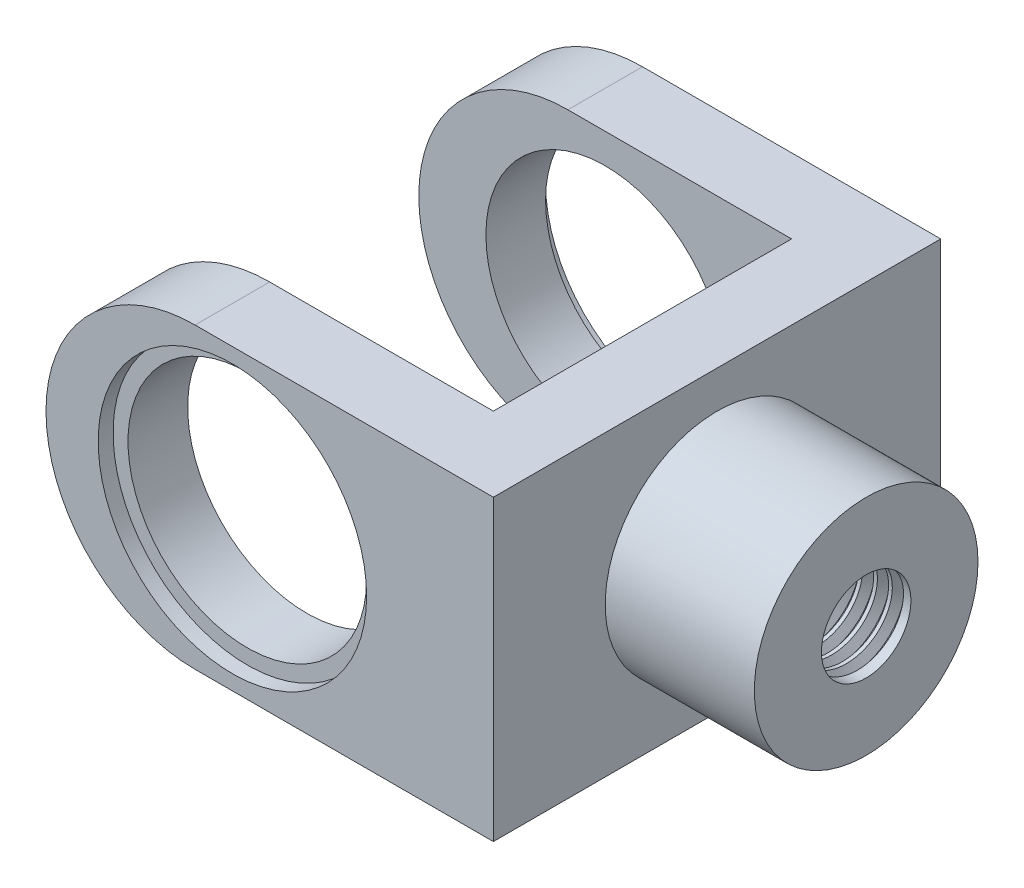
SolidWorks part; units mm, degrees
material "7075-T6 (SN)"
ref_plane "Ön Düzlem" through (0, 0, 0) normal (0, 0, 1) x (1, 0, 0)
ref_plane "Üst Düzlem" through (0, 0, 0) normal (0, 1, 0) x (1, 0, 0)
ref_plane "Sağ Düzlem" through (0, 0, 0) normal (1, 0, 0) x (0, 0, -1)
sketch "Çizim1" plane through (0, 0, 0) normal (0, 0, 1) x (1, 0, 0)
  line L0 (0, 10) -> (20, 10)
  line L1 (0, -10) -> (20, -10)
  line L2 (20, -10) -> (20, 10)
  line L3 (20, 0) -> (0, 0) construction
  line L4 (15, 10) -> (15, -10) construction
  arc A0 (0, 10) -> (0, -10) centre (0, 0) ccw
  circle A1 centre (2.5, 0) radius 4
  dimension "D1" = 20
  dimension "D2" = 20
  dimension "D3" = 8
  dimension "D4" = 5
  dimension "D5" = 12.5
extrude "Yükseklik-Ekstrüzyon1" add sketch "Çizim1" along normal blind 30
sketch "Çizim2" plane through (20, 0, 0) normal (1, 0, 0) x (0, 0, -1)
  line L2 (-25, -10) -> (-25, 10)
  line L3 (-25, -10) -> (-25, 10)
  line L4 (-25, 10) -> (-5, 10)
  line L5 (-5, -10) -> (-5, 10)
  line L6 (-5, -10) -> (-5, 10)
  line L7 (-25, -10) -> (-5, -10)
  dimension "D1" = 5
  dimension "D2" = 5
extrude "Kes-Ekstrüzyon1" cut sketch "Çizim2" against normal blind 51
sketch "Çizim3" plane through (20, 0, 0) normal (1, 0, 0) x (0, 0, -1)
  line L0 (-30, 10) -> (0, 10)
  line L1 (0, 10) -> (0, -10)
  line L2 (0, -10) -> (-30, -10)
  line L3 (-30, -10) -> (-30, 10)
extrude "Yükseklik-Ekstrüzyon2" add sketch "Çizim3" against normal blind 5
sketch "Çizim4" plane through (20, 0, 0) normal (1, 0, 0) x (0, 0, -1)
  line L0 (0, -10) -> (-30, 10) construction
  circle A0 centre (-15, 0) radius 3 construction
  circle A1 centre (-15, 0) radius 7.5
  dimension "D1" = 6
  dimension "D2" = 15
extrude "Yükseklik-Ekstrüzyon3" add sketch "Çizim4" along normal blind 10
sketch "Çizim7" plane through (30, 0, 0) normal (1, 0, 0) x (0, 0, -1)
  circle A0 centre (-15, 0) radius 3
  dimension "D1" = 6
extrude "Kes-Ekstrüzyon2" cut sketch "Çizim7" against normal blind 10
sketch "Sketch1" plane through (0, 0, 30) normal (0, 0, 1) x (1, 0, 0)
  circle A0 centre (2.5, 0) radius 8
  dimension "D1" = 16
extrude "Cut-Extrude1" cut sketch "Sketch1" against normal blind 33
sketch "Sketch2" plane through (0, 0, 30) normal (0, 0, 1) x (1, 0, 0)
  circle A0 centre (2.5, 0) radius 9
  dimension "D1" = 18
extrude "Cut-Extrude2" cut sketch "Sketch2" against normal blind 1
sketch "Sketch3" plane through (0, 0, 0) normal (0, 0, -1) x (-1, 0, 0)
  circle A0 centre (-2.5, 0) radius 9
  dimension "D1" = 18
extrude "Cut-Extrude3" cut sketch "Sketch3" against normal blind 1
thread "Thread1" pitch 1 method cut profile "Thread Profile1" start angle 0, offset 0, length 0, pitch 1, diameter 6
ref_plane "Plane1" through (30, 0, 18) normal (0, -1, 0) x (0, 0, 1)
sketch "Thread Profile1" plane through (30, 0, 18) normal (0, -1, 0) x (0, 0, 1)
  line L0 (0, 0) -> (0, 1) construction
  line L1 (0, 0) -> (0.5413, 0.3125)
  line L2 (0.5413, 0.3125) -> (0.5413, 0.4375)
  line L3 (0.5413, 0.4375) -> (0, 0.75)
  line L4 (0.5413, 0.375) -> (0, 0.375) construction
  line L11 (0, 0) -> (0, 0.75)
  point P2 (0, 0)
  dimension "Pitch" = 1
  dimension "Profile_Angle" = 60
  dimension "Profile_Land" = 0.125
  dimension "Profile_Height" = 0.5413
